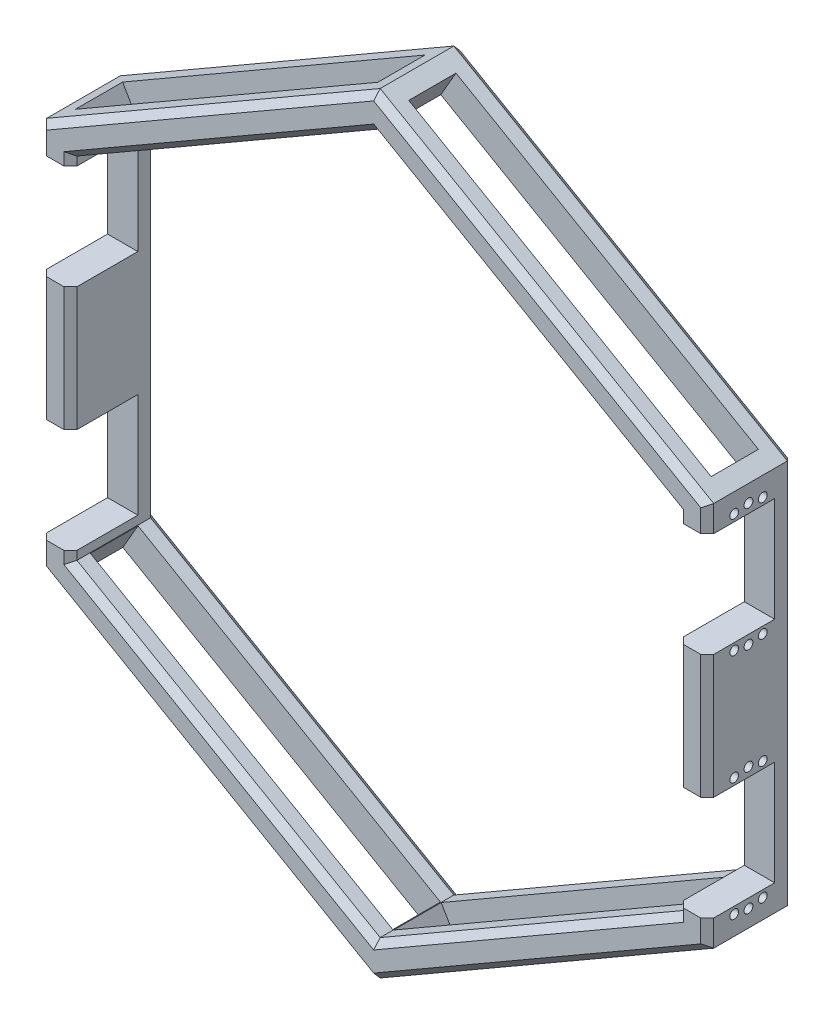
SolidWorks part; units mm, degrees
material "Caoutchouc"
ref_plane "Plan de face" through (0, 0, 0) normal (0, 0, 1) x (1, 0, 0)
ref_plane "Plan de dessus" through (0, 0, 0) normal (0, 1, 0) x (1, 0, 0)
ref_plane "Plan de droite" through (0, 0, 0) normal (1, 0, 0) x (0, 0, -1)
sketch "Esquisse1" plane through (0, 0, 0) normal (0, 0, 1) x (1, 0, 0)
  line L0 (-77, -44.456) -> (0, 0)
  line L1 (0, -8.0829) -> (70, -48.4974)
  line L2 (-77, -44.456) -> (-77, -133.3679)
  line L3 (70, -48.4974) -> (70, -129.3265)
  line L4 (77, -44.456) -> (77, -133.3679)
  line L5 (0, 0) -> (77, -44.456)
  line L6 (-77, -133.3679) -> (0, -177.8239)
  line L7 (0, -177.8239) -> (77, -133.3679)
  line L8 (70, -129.3265) -> (0, -169.741)
  line L9 (0, -169.741) -> (-70, -129.3265)
  line L10 (-70, -129.3265) -> (-70, -48.4974)
  line L11 (-70, -48.4974) -> (0, -8.0829)
  dimension "D1" = 120
  dimension "D2" = 120
  dimension "D3" = 7
  dimension "D4" = 7
  dimension "D5" = 7
  dimension "D6" = 70
extrude "Boss.-Extru.1" add sketch "Esquisse1" along normal blind 20
chamfer "Chanfrein1" distance 1.5 angle 45 24 edges at (-38.5, -155.5959, 20) (-77, -88.9119, 20) (-38.5, -22.228, 20) (38.5, -22.228, 20) (38.5, -155.5959, 20) (77, -88.9119, 20) (-77, -88.9119, 0) (-38.5, -155.5959, 0) (38.5, -155.5959, 0) (77, -88.9119, 0) (38.5, -22.228, 0) (-38.5, -22.228, 0) (-35, -149.5337, 20) (-70, -88.9119, 20) (-35, -28.2902, 20) (35, -28.2902, 20) (70, -88.9119, 20) (35, -149.5337, 20) (-35, -149.5337, 0) (35, -149.5337, 0) (70, -88.9119, 0) (35, -28.2902, 0) (-70, -88.9119, 0) (-35, -28.2902, 0)
sketch "Esquisse4" plane through (-70, 0, 0) normal (1, 0, 0) x (0, 0, -1)
  line L0 (-18.5, -48.4974) -> (-1.5, -48.4974) construction
  line L1 (-21.8389, -50.4974) -> (-4.435, -50.4974)
  line L2 (-21.8389, -50.4974) -> (-21.8389, -74.6274)
  line L3 (-21.8389, -74.6274) -> (-4.435, -74.6274)
  line L4 (-4.435, -50.4974) -> (-4.435, -74.6274)
  line L7 (-36.7449, -88.9119) -> (25.0579, -88.9119) construction
  line L8 (-18.5, -129.3265) -> (-1.5, -129.3265) construction
  line L9 (-21.8389, -127.3265) -> (-4.435, -127.3265)
  line L10 (-4.435, -127.3265) -> (-4.435, -103.1965)
  line L11 (-21.8389, -127.3265) -> (-21.8389, -103.1965)
  line L12 (-21.8389, -103.1965) -> (-4.435, -103.1965)
  dimension "D1" = 2
  dimension "D4" = 24.13
extrude "Enlèv. mat.-Extru.1" cut sketch "Esquisse4" against normal blind 10 and the other way through all
sketch "Esquisse6" plane through (-77, 0, 0) normal (-1, 0, 0) x (0, 0, 1)
  line L0 (32.243, -62.5529) -> (-9.9857, -62.5529) construction
  line L1 (16.319, -50.6784) -> (10.4996, -50.6784) construction
  line L2 (16.319, -74.4274) -> (4.635, -74.4274) construction
  line L3 (-15.4771, -88.9119) -> (37.6916, -88.9119) construction
  line L4 (18.5, -74.6274) -> (4.435, -74.6274) construction
  line L5 (4.435, -103.1965) -> (18.5, -103.1965) construction
  circle A0 centre (13.779, -48.9004) radius 1.016
  circle A1 centre (10.477, -48.3924) radius 1.016
  circle A2 centre (7.175, -48.9004) radius 1.016
  circle A3 centre (7.175, -76.2054) radius 1.016
  circle A4 centre (10.477, -76.7134) radius 1.016
  circle A5 centre (13.779, -76.2054) radius 1.016
  circle A6 centre (7.175, -128.9235) radius 1.016
  circle A7 centre (10.477, -129.4315) radius 1.016
  circle A8 centre (13.779, -128.9235) radius 1.016
  circle A9 centre (7.175, -101.6185) radius 1.016
  circle A10 centre (10.477, -101.1105) radius 1.016
  circle A11 centre (13.779, -101.6185) radius 1.016
  dimension "D1" = 2.032
extrude "Enlèv. mat.-Extru.2" cut sketch "Esquisse6" against normal blind 5
ref_plane "Plan1" through (0, 0, 0) normal (1, 0, 0) x (0, 0, -1)
mirror "Symétrie1" about plane through (0, 0, 0) normal (1, 0, 0) of "Enlèv. mat.-Extru.2"
sketch "Esquisse8" plane through (0, 0, 0) normal (-0.5, 0.866, 0) x (0, 0, 1)
  line L0 (18.5, -88.9119) -> (1.5, -88.9119) construction
  line L1 (4.55, -84.7619) -> (15.45, -84.7619)
  line L2 (4.55, -84.7619) -> (4.55, -4.15)
  line L3 (4.55, -4.15) -> (15.45, -4.15)
  line L4 (15.45, -84.7619) -> (15.45, -4.15)
  line L5 (18.5, -88.9119) -> (18.5, 0) construction
  line L6 (1.5, 0) -> (1.5, -88.9119) construction
  line L7 (18.5, 0) -> (1.5, 0) construction
  dimension "D1" = 4.15
  dimension "D2" = 3.05
  dimension "D3" = 3.05
  dimension "D4" = 4.15
extrude "Enlèv. mat.-Extru.3" cut sketch "Esquisse8" against normal up to surface (7 mm away) up to face at (-35, -28.2902, 10)
sketch "Esquisse9" plane through (0, 0, 0) normal (0.5, 0.866, 0) x (0, 0, -1)
  line L0 (-15.45, 2.075) -> (-4.55, 2.075) construction
  line L1 (-15.5, -84.7619) -> (-4.6, -84.7619)
  line L2 (-15.5, -84.7619) -> (-15.5, -4.15)
  line L3 (-15.5, -4.15) -> (-4.6, -4.15)
  line L4 (-4.6, -84.7619) -> (-4.6, -4.15)
  line L6 (-18.5, 0) -> (-1.5, 0) construction
  line L7 (-18.5, 0) -> (-18.5, -88.9119) construction
  line L8 (-18.5, -88.9119) -> (-1.5, -88.9119) construction
  dimension "D1" = 4.15
  dimension "D2" = 3
  dimension "D3" = 4.15
extrude "Enlèv. mat.-Extru.4" cut sketch "Esquisse9" against normal up to surface (7 mm away) up to face at (35, -28.2902, 10)
sketch "Esquisse10" plane through (-77, -133.3679, 0) normal (-0.5, -0.866, 0) x (0, 0, 1)
  line L0 (15.5, -4.15) -> (15.5, -84.7619) construction
  line L1 (4.5, -84.7619) -> (15.5, -84.7619)
  line L2 (4.5, -84.7619) -> (4.5, -4.15)
  line L3 (4.5, -4.15) -> (15.5, -4.15)
  line L4 (15.5, -84.7619) -> (15.5, -4.15)
  line L5 (15.5, -84.7619) -> (4.6, -84.7619) construction
  line L6 (18.5, -88.9119) -> (1.5, -88.9119) construction
  line L7 (1.5, 0) -> (1.5, -88.9119) construction
  line L8 (18.5, -88.9119) -> (18.5, 0) construction
  dimension "D1" = 4.15
  dimension "D2" = 3
  dimension "D3" = 3
sketch "Esquisse11" plane through (77, -133.3679, 0) normal (0.5, -0.866, 0) x (0, 0, -1)
  line L1 (-15.5, -4.15) -> (-4.5, -4.15)
  line L2 (-15.5, -4.15) -> (-15.5, -84.7619)
  line L3 (-15.5, -84.7619) -> (-4.5, -84.7619)
  line L4 (-4.5, -4.15) -> (-4.5, -84.7619)
  line L6 (-4.5, -90.9869) -> (-15.5, -90.9869) construction
  line L7 (-4.55, -4.15) -> (-4.55, -84.7619) construction
  line L8 (-18.5, 0) -> (-1.5, 0) construction
  line L9 (-1.5, -88.9119) -> (-1.5, 0) construction
  dimension "D1" = 4.15
  dimension "D2" = 3
extrude "Enlèv. mat.-Extru.5" cut sketch "Esquisse11" against normal up to surface (7 mm away) up to face at (35, -149.5337, 10)
extrude "Enlèv. mat.-Extru.6" cut sketch "Esquisse10" against normal up to surface (7 mm away) up to face at (-35, -149.5337, 10)
